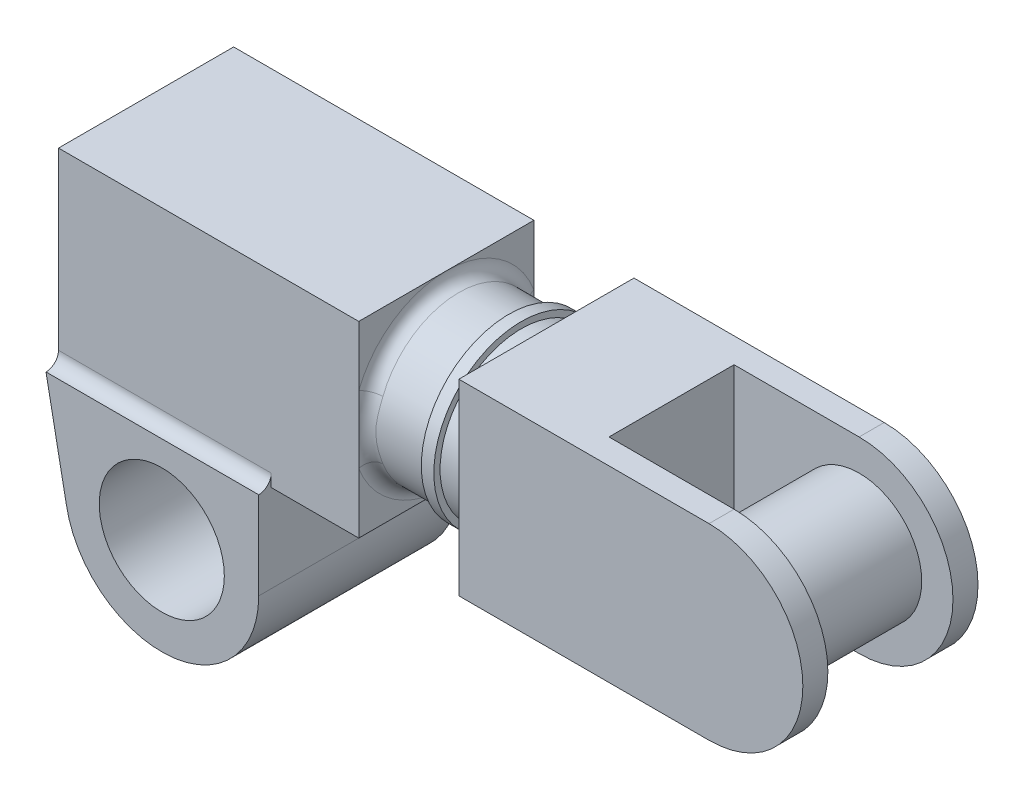
SolidWorks part; units mm, degrees
ref_plane "前视基准面" through (0, 0, 0) normal (0, 0, 1) x (1, 0, 0)
ref_plane "上视基准面" through (0, 0, 0) normal (0, 1, 0) x (1, 0, 0)
ref_plane "右视基准面" through (0, 0, 0) normal (1, 0, 0) x (0, 0, -1)
sketch "草图1" plane through (0, 0, 0) normal (1, 0, 0) x (0, 0, -1)
  line L1 (-70, 75) -> (70, 75)
  line L2 (-70, 75) -> (-70, -75)
  line L3 (-70, -75) -> (70, -75)
  line L4 (70, 75) -> (70, -75)
  line L5 (-70, 75) -> (70, -75) construction
  line L6 (-70, -75) -> (70, 75) construction
  point P0 (0, 0)
  dimension "D1" = 150
  dimension "D2" = 140
extrude "凸台-拉伸1" add sketch "草图1" along normal blind 240
sketch "草图2" plane through (240, 0, 0) normal (1, 0, 0) x (0, 0, -1)
  circle A0 centre (0, 0) radius 65
  dimension "D1" = 130
extrude "凸台-拉伸2" add sketch "草图2" along normal blind 50
sketch "草图3" plane through (290, 0, 0) normal (1, 0, 0) x (0, 0, -1)
  circle A0 centre (0, 0) radius 70
  dimension "D1" = 140
extrude "凸台-拉伸3" add sketch "草图3" along normal blind 10
sketch "草图4" plane through (0, 0, 0) normal (0, 0, 1) x (1, 0, 0)
  line L0 (0, -75) -> (16.2188, -158.4383)
  line L1 (0, 75) -> (0, -75) construction
  line L2 (170.0448, -145) -> (170.0448, -75)
  line L3 (240, -75) -> (0, -75) construction
  line L4 (0, -75) -> (170.0448, -75)
  arc A0 (16.2188, -158.4383) -> (170.0448, -145) centre (92.5448, -145) ccw
  circle A1 centre (92.5448, -145) radius 50
  dimension "D1" = 155
  dimension "D2" = 100
  dimension "D3" = 191
  dimension "D4" = 85
  dimension "D5" = 70
extrude "凸台-拉伸4" add sketch "草图4" along normal mid plane 160
fillet "圆角1" radius 10 3 edges at (85.0224, -75, -70) (240, 0, -65) (85.0224, -75, 70)
sketch "草图5" plane through (300, 0, 0) normal (1, 0, 0) x (0, 0, -1)
  circle A0 centre (0, 0) radius 65
  dimension "D1" = 130
extrude "凸台-拉伸5" add sketch "草图5" along normal blind 20
sketch "草图6" plane through (0, 0, 0) normal (0, 0, 1) x (1, 0, 0)
  line L0 (520, 75) -> (320, 75)
  line L1 (320, 75) -> (320, -75)
  line L2 (320, -75) -> (520, -75)
  line L3 (320, -65) -> (320, 65) construction
  arc A0 (520, -75) -> (520, 75) centre (520, 0) ccw
  dimension "D1" = 150
  dimension "D2" = 200
extrude "凸台-拉伸6" add sketch "草图6" along normal mid plane 140
sketch "草图7" plane through (0, 0, 0) normal (0, 0, 1) x (1, 0, 0)
  line L0 (520, 75) -> (420, 75)
  line L1 (520, 75) -> (320, 75) construction
  line L2 (420, 75) -> (420, -75)
  line L3 (320, -75) -> (520, -75) construction
  line L4 (420, -75) -> (520, -75)
  arc A0 (520, -75) -> (520, 75) centre (520, 0) ccw construction
  arc A1 (520, -75) -> (520, 75) centre (520, 0) ccw
  dimension "D1" = 100
extrude "切除-拉伸1" cut sketch "草图7" against normal mid plane 100
sketch "草图8" plane through (0, 0, -50) normal (0, 0, 1) x (1, 0, 0)
  circle A0 centre (520, 0) radius 50
  dimension "D1" = 100
extrude "凸台-拉伸7" add sketch "草图8" along normal up to next
